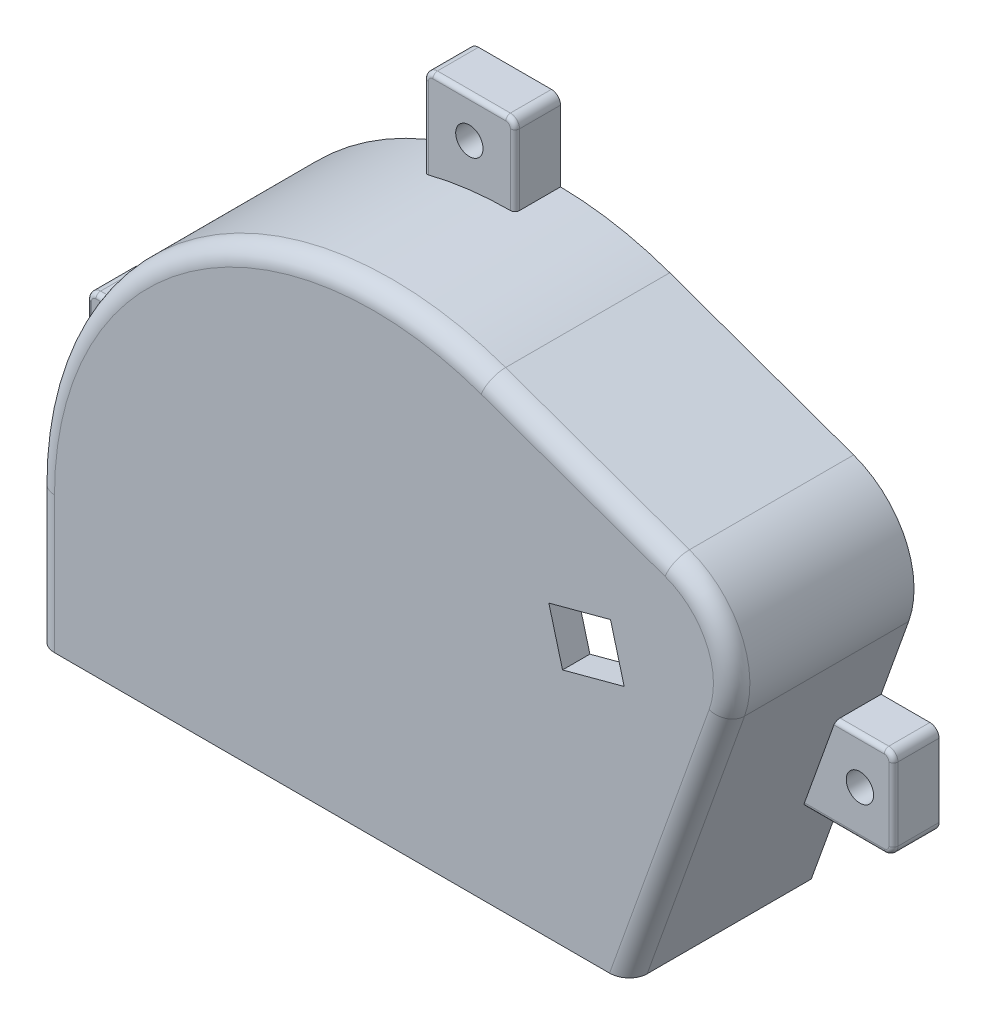
SolidWorks part; units mm, degrees
ref_plane "Plan de face" through (0, 0, 0) normal (0, 0, 1) x (1, 0, 0)
ref_plane "Plan de dessus" through (0, 0, 0) normal (0, 1, 0) x (1, 0, 0)
ref_plane "Plan de droite" through (0, 0, 0) normal (1, 0, 0) x (0, 0, -1)
sketch "Esquisse1" plane through (0, 0, 0) normal (0, 0, 1) x (1, 0, 0)
  line L1 (-27.5, 15) -> (-27.5, 5)
  line L8 (-32.5, 11.3798) -> (-32.5, 0)
  line L9 (-32.5, 0) -> (32.5, 0)
  line L10 (40.1606, 21.3798) -> (43.1847, 29.8198)
  line L11 (37.1439, 42.6068) -> (16.9805, 49.8316)
  line L15 (-27.5, 5) -> (28.9803, 5)
  line L17 (28.9803, 5) -> (38.4778, 31.5063)
  line L19 (35.4573, 37.8998) -> (15.2939, 45.1246)
  line L49 (5, 51.9966) -> (5, 59.7596)
  line L51 (4, 60.7596) -> (-4, 60.7596)
  line L53 (-5, 59.7596) -> (-5, 50.7596)
  line L55 (-31.9458, 21.3798) -> (-40.9458, 21.3798)
  line L57 (-41.9458, 20.3798) -> (-41.9458, 12.3798)
  line L59 (-40.9458, 11.3798) -> (-32.5, 11.3798)
  line L61 (32.5, 0) -> (36.5775, 11.3798)
  line L63 (36.5775, 11.3798) -> (45.5082, 11.3798)
  line L65 (46.5082, 12.3798) -> (46.5082, 20.3798)
  line L67 (45.5082, 21.3798) -> (40.1606, 21.3798)
  arc A1 (15.2939, 45.1246) -> (-27.5, 15) centre (4.5, 15) ccw
  arc A4 (43.1847, 29.8198) -> (37.1439, 42.6068) centre (33.7708, 33.1929) ccw
  arc A5 (16.9805, 49.8316) -> (5, 51.9966) centre (4.5, 15) ccw
  arc A9 (38.4778, 31.5063) -> (35.4573, 37.8998) centre (33.7708, 33.1929) ccw
  arc A29 (5, 59.7596) -> (4, 60.7596) centre (4, 59.7596) ccw
  arc A31 (-4, 60.7596) -> (-5, 59.7596) centre (-4, 59.7596) ccw
  arc A33 (-5, 50.7596) -> (-31.9458, 21.3798) centre (4.5, 15) ccw
  arc A35 (-40.9458, 21.3798) -> (-41.9458, 20.3798) centre (-40.9458, 20.3798) ccw
  arc A37 (-41.9458, 12.3798) -> (-40.9458, 11.3798) centre (-40.9458, 12.3798) ccw
  arc A39 (45.5082, 11.3798) -> (46.5082, 12.3798) centre (45.5082, 12.3798) ccw
  arc A41 (46.5082, 20.3798) -> (45.5082, 21.3798) centre (45.5082, 20.3798) ccw
extrude "Boss.-Extru.1" add sketch "Esquisse1" along normal blind 20
sketch "Esquisse5" plane through (0, 0, 20) normal (0, 0, 1) x (1, 0, 0)
  line L5 (5, 51.9966) -> (5, 59.7596)
  line L6 (-32.5, 11.3798) -> (-32.5, 0)
  line L7 (-32.5, 0) -> (32.5, 0)
  line L8 (40.1606, 21.3798) -> (43.1847, 29.8198)
  line L9 (37.1439, 42.6068) -> (16.9805, 49.8316)
  line L11 (-32.5, 11.3798) -> (-32.5, 0)
  line L12 (-32.5, 0) -> (32.5, 0)
  line L13 (40.1606, 21.3798) -> (43.1847, 29.8198)
  line L14 (37.1439, 42.6068) -> (16.9805, 49.8316)
  line L24 (5, 51.9966) -> (5, 59.7596)
  line L25 (4, 60.7596) -> (-4, 60.7596)
  line L26 (4, 60.7596) -> (-4, 60.7596)
  line L27 (-5, 59.7596) -> (-5, 50.7596)
  line L28 (-5, 59.7596) -> (-5, 50.7596)
  line L29 (-31.9458, 21.3798) -> (-40.9458, 21.3798)
  line L30 (-31.9458, 21.3798) -> (-40.9458, 21.3798)
  line L31 (-41.9458, 20.3798) -> (-41.9458, 12.3798)
  line L32 (-41.9458, 20.3798) -> (-41.9458, 12.3798)
  line L33 (-40.9458, 11.3798) -> (-32.5, 11.3798)
  line L34 (-40.9458, 11.3798) -> (-32.5, 11.3798)
  line L35 (32.5, 0) -> (36.5775, 11.3798)
  line L36 (32.5, 0) -> (36.5775, 11.3798)
  line L37 (36.5775, 11.3798) -> (45.5082, 11.3798)
  line L38 (36.5775, 11.3798) -> (45.5082, 11.3798)
  line L39 (46.5082, 12.3798) -> (46.5082, 20.3798)
  line L40 (46.5082, 12.3798) -> (46.5082, 20.3798)
  line L41 (45.5082, 21.3798) -> (40.1606, 21.3798)
  line L42 (45.5082, 21.3798) -> (40.1606, 21.3798)
  arc A2 (-5, 50.7596) -> (-31.9458, 21.3798) centre (4.5, 15) ccw
  arc A3 (43.1847, 29.8198) -> (37.1439, 42.6068) centre (33.7708, 33.1929) ccw
  arc A4 (-5, 50.7596) -> (-31.9458, 21.3798) centre (4.5, 15) ccw
  arc A5 (43.1847, 29.8198) -> (37.1439, 42.6068) centre (33.7708, 33.1929) ccw
  arc A13 (16.9805, 49.8316) -> (5, 51.9966) centre (4.5, 15) ccw
  arc A14 (16.9805, 49.8316) -> (5, 51.9966) centre (4.5, 15) ccw
  arc A15 (5, 59.7596) -> (4, 60.7596) centre (4, 59.7596) ccw
  arc A16 (5, 59.7596) -> (4, 60.7596) centre (4, 59.7596) ccw
  arc A17 (-4, 60.7596) -> (-5, 59.7596) centre (-4, 59.7596) ccw
  arc A18 (-4, 60.7596) -> (-5, 59.7596) centre (-4, 59.7596) ccw
  arc A19 (-40.9458, 21.3798) -> (-41.9458, 20.3798) centre (-40.9458, 20.3798) ccw
  arc A20 (-40.9458, 21.3798) -> (-41.9458, 20.3798) centre (-40.9458, 20.3798) ccw
  arc A21 (-41.9458, 12.3798) -> (-40.9458, 11.3798) centre (-40.9458, 12.3798) ccw
  arc A22 (-41.9458, 12.3798) -> (-40.9458, 11.3798) centre (-40.9458, 12.3798) ccw
  arc A23 (45.5082, 11.3798) -> (46.5082, 12.3798) centre (45.5082, 12.3798) ccw
  arc A24 (45.5082, 11.3798) -> (46.5082, 12.3798) centre (45.5082, 12.3798) ccw
  arc A25 (46.5082, 20.3798) -> (45.5082, 21.3798) centre (45.5082, 20.3798) ccw
  arc A26 (46.5082, 20.3798) -> (45.5082, 21.3798) centre (45.5082, 20.3798) ccw
  dimension "D1" = 0
extrude "Boss.-Extru.3" add sketch "Esquisse5" against normal blind 3
sketch "Esquisse6" plane through (0, 0, 17) normal (0, 0, -1) x (-1, 0, 0)
  line L8 (-30.4796, 33.6382) -> (-23.7182, 31.8265)
  line L9 (-23.7182, 31.8265) -> (-25.2193, 26.2241)
  line L10 (-25.2193, 26.2241) -> (-31.9808, 28.0358)
  line L11 (-31.9808, 28.0358) -> (-30.4796, 33.6382)
extrude "Enlèv. mat.-Extru.3" cut sketch "Esquisse6" against normal blind 3
sketch "Esquisse8" plane through (0, 0, 0) normal (0, 0, -1) x (-1, 0, 0)
  line L0 (-36.5775, 11.3798) -> (-40.1606, 21.3798)
  line L1 (-36.5775, 11.3798) -> (-40.1606, 21.3798)
  line L2 (-36.5775, 11.3798) -> (-40.1606, 21.3798)
  line L3 (32.5, 15) -> (32.5, 11.3798)
  line L14 (-43.1847, 29.8198) -> (-40.1606, 21.3798)
  line L15 (-40.1606, 21.3798) -> (-45.5082, 21.3798)
  line L16 (-46.5082, 20.3798) -> (-46.5082, 12.3798)
  line L17 (-45.5082, 11.3798) -> (-36.5775, 11.3798)
  line L18 (-36.5775, 11.3798) -> (-32.5, 0)
  line L19 (-32.5, 0) -> (32.5, 0)
  line L20 (32.5, 0) -> (32.5, 11.3798)
  line L21 (32.5, 11.3798) -> (40.9458, 11.3798)
  line L22 (41.9458, 12.3798) -> (41.9458, 20.3798)
  line L23 (40.9458, 21.3798) -> (31.9458, 21.3798)
  line L24 (5, 50.7596) -> (5, 59.7596)
  line L25 (4, 60.7596) -> (-4, 60.7596)
  line L26 (-5, 59.7596) -> (-5, 51.9966)
  line L27 (-16.9805, 49.8316) -> (-37.1439, 42.6068)
  line L29 (-40.1606, 21.3798) -> (-45.5082, 21.3798)
  line L30 (-46.5082, 20.3798) -> (-46.5082, 12.3798)
  line L31 (-45.5082, 11.3798) -> (-36.5775, 11.3798)
  line L35 (32.5, 11.3798) -> (40.9458, 11.3798)
  line L36 (41.9458, 12.3798) -> (41.9458, 20.3798)
  line L37 (40.9458, 21.3798) -> (31.9458, 21.3798)
  line L38 (5, 50.7596) -> (5, 59.7596)
  line L39 (4, 60.7596) -> (-4, 60.7596)
  line L40 (-5, 59.7596) -> (-5, 51.9966)
  arc A0 (5, 50.7596) -> (-5, 51.9966) centre (-4.5, 15) ccw
  arc A1 (32.5, 15) -> (31.9458, 21.3798) centre (-4.5, 15) ccw
  circle A2 centre (37.2229, 16.3798) radius 1.5
  circle A3 centre (0, 56.3781) radius 1.5
  circle A4 centre (-42.8344, 16.3798) radius 1.5
  arc A9 (-37.1439, 42.6068) -> (-43.1847, 29.8198) centre (-33.7708, 33.1929) ccw
  arc A10 (-45.5082, 21.3798) -> (-46.5082, 20.3798) centre (-45.5082, 20.3798) ccw
  arc A11 (-46.5082, 12.3798) -> (-45.5082, 11.3798) centre (-45.5082, 12.3798) ccw
  arc A12 (40.9458, 11.3798) -> (41.9458, 12.3798) centre (40.9458, 12.3798) ccw
  arc A13 (41.9458, 20.3798) -> (40.9458, 21.3798) centre (40.9458, 20.3798) ccw
  arc A14 (31.9458, 21.3798) -> (5, 50.7596) centre (-4.5, 15) ccw
  arc A15 (5, 59.7596) -> (4, 60.7596) centre (4, 59.7596) ccw
  arc A16 (-4, 60.7596) -> (-5, 59.7596) centre (-4, 59.7596) ccw
  arc A17 (-5, 51.9966) -> (-16.9805, 49.8316) centre (-4.5, 15) ccw
  arc A19 (-45.5082, 21.3798) -> (-46.5082, 20.3798) centre (-45.5082, 20.3798) ccw
  arc A20 (-46.5082, 12.3798) -> (-45.5082, 11.3798) centre (-45.5082, 12.3798) ccw
  arc A21 (40.9458, 11.3798) -> (41.9458, 12.3798) centre (40.9458, 12.3798) ccw
  arc A22 (41.9458, 20.3798) -> (40.9458, 21.3798) centre (40.9458, 20.3798) ccw
  arc A24 (5, 59.7596) -> (4, 60.7596) centre (4, 59.7596) ccw
  arc A25 (-4, 60.7596) -> (-5, 59.7596) centre (-4, 59.7596) ccw
  dimension "D1" = 0
sketch "Esquisse9" plane through (0, 0, 20) normal (0, 0, 1) x (1, 0, 0)
  line L0 (36.5775, 11.3798) -> (40.1606, 21.3798) construction
  line L1 (36.5775, 11.3798) -> (40.1606, 21.3798) construction
  line L2 (36.5775, 11.3798) -> (40.1606, 21.3798) construction
  line L3 (5, 51.9966) -> (5, 59.7596)
  line L4 (-31.9458, 21.3798) -> (-40.9458, 21.3798)
  line L5 (-32.5, 11.3798) -> (-32.5, 15)
  line L6 (-40.9458, 11.3798) -> (-32.5, 11.3798)
  line L7 (-41.9458, 20.3798) -> (-41.9458, 12.3798)
  line L8 (-31.9458, 21.3798) -> (-40.9458, 21.3798)
  line L9 (-32.5, 11.3798) -> (-32.5, 15)
  line L10 (-40.9458, 11.3798) -> (-32.5, 11.3798)
  line L11 (-41.9458, 20.3798) -> (-41.9458, 12.3798)
  line L12 (4, 60.7596) -> (-4, 60.7596)
  line L13 (-5, 59.7596) -> (-5, 50.7596)
  line L14 (5, 51.9966) -> (5, 59.7596)
  line L15 (4, 60.7596) -> (-4, 60.7596)
  line L16 (-5, 59.7596) -> (-5, 50.7596)
  line L17 (40.1606, 21.3798) -> (45.5082, 21.3798) construction
  line L18 (46.5082, 20.3798) -> (46.5082, 12.3798) construction
  line L19 (45.5082, 11.3798) -> (36.5775, 11.3798) construction
  line L20 (36.5775, 11.3798) -> (40.1606, 21.3798)
  line L21 (36.5775, 11.3798) -> (40.1606, 21.3798)
  line L22 (36.5775, 11.3798) -> (40.1606, 21.3798)
  line L23 (40.1606, 21.3798) -> (45.5082, 21.3798)
  line L24 (46.5082, 20.3798) -> (46.5082, 12.3798)
  line L25 (45.5082, 11.3798) -> (36.5775, 11.3798)
  arc A0 (46.5082, 20.3798) -> (45.5082, 21.3798) centre (45.5082, 20.3798) ccw construction
  arc A7 (45.5082, 11.3798) -> (46.5082, 12.3798) centre (45.5082, 12.3798) ccw construction
  arc A8 (46.5082, 20.3798) -> (45.5082, 21.3798) centre (45.5082, 20.3798) ccw
  arc A9 (-31.9458, 21.3798) -> (-32.5, 15) centre (4.5, 15) ccw
  arc A10 (-41.9458, 12.3798) -> (-40.9458, 11.3798) centre (-40.9458, 12.3798) ccw
  arc A11 (-40.9458, 21.3798) -> (-41.9458, 20.3798) centre (-40.9458, 20.3798) ccw
  arc A12 (-31.9458, 21.3798) -> (-32.5, 15) centre (4.5, 15) ccw
  arc A13 (-41.9458, 12.3798) -> (-40.9458, 11.3798) centre (-40.9458, 12.3798) ccw
  arc A14 (-40.9458, 21.3798) -> (-41.9458, 20.3798) centre (-40.9458, 20.3798) ccw
  arc A15 (5, 59.7596) -> (4, 60.7596) centre (4, 59.7596) ccw
  arc A16 (-4, 60.7596) -> (-5, 59.7596) centre (-4, 59.7596) ccw
  arc A17 (5, 51.9966) -> (-5, 50.7596) centre (4.5, 15) ccw
  arc A18 (5, 59.7596) -> (4, 60.7596) centre (4, 59.7596) ccw
  arc A19 (-4, 60.7596) -> (-5, 59.7596) centre (-4, 59.7596) ccw
  arc A20 (5, 51.9966) -> (-5, 50.7596) centre (4.5, 15) ccw
  arc A21 (45.5082, 11.3798) -> (46.5082, 12.3798) centre (45.5082, 12.3798) ccw
  dimension "D4" = 0
  dimension "D5" = 0
extrude "Enlèv. mat.-Extru.4" cut sketch "Esquisse9" against normal blind 15
sketch "Esquisse10" plane through (0, 0, 5) normal (0, 0, 1) x (1, 0, 0)
  circle A0 centre (-37.2229, 16.3798) radius 1.5 construction
  circle A1 centre (-37.2229, 16.3798) radius 1.5
  circle A2 centre (0, 56.3781) radius 1.5 construction
  circle A3 centre (0, 56.3781) radius 1.5
  circle A4 centre (42.8344, 16.3798) radius 1.5 construction
  circle A5 centre (42.8344, 16.3798) radius 1.5
extrude "Enlèv. mat.-Extru.5" cut sketch "Esquisse10" against normal through all
fillet "Congé1" radius 2 5 edges at (37.8424, 14.9099, 20) (42.8126, 37.4644, 20) (27.0622, 46.2192, 20) (-32.5, 7.5, 20) (-16.7981, 45.2554, 20)
fillet "Congé2" radius 0.5 15 edges at (41.0428, 11.3798, 5) (46.2153, 11.6727, 5) (46.5082, 16.3798, 5) (46.2153, 21.0869, 5) (5, 55.8781, 5) (4.7071, 60.4667, 5) (0, 60.7596, 5) (-4.7071, 60.4667, 5) (-36.4458, 21.3798, 5) (-41.6529, 21.0869, 5) (-41.9458, 16.3798, 5) (-41.6529, 11.6727, 5) (42.8344, 21.3798, 5) (-5, 55.2596, 5) (-36.7229, 11.3798, 5)
